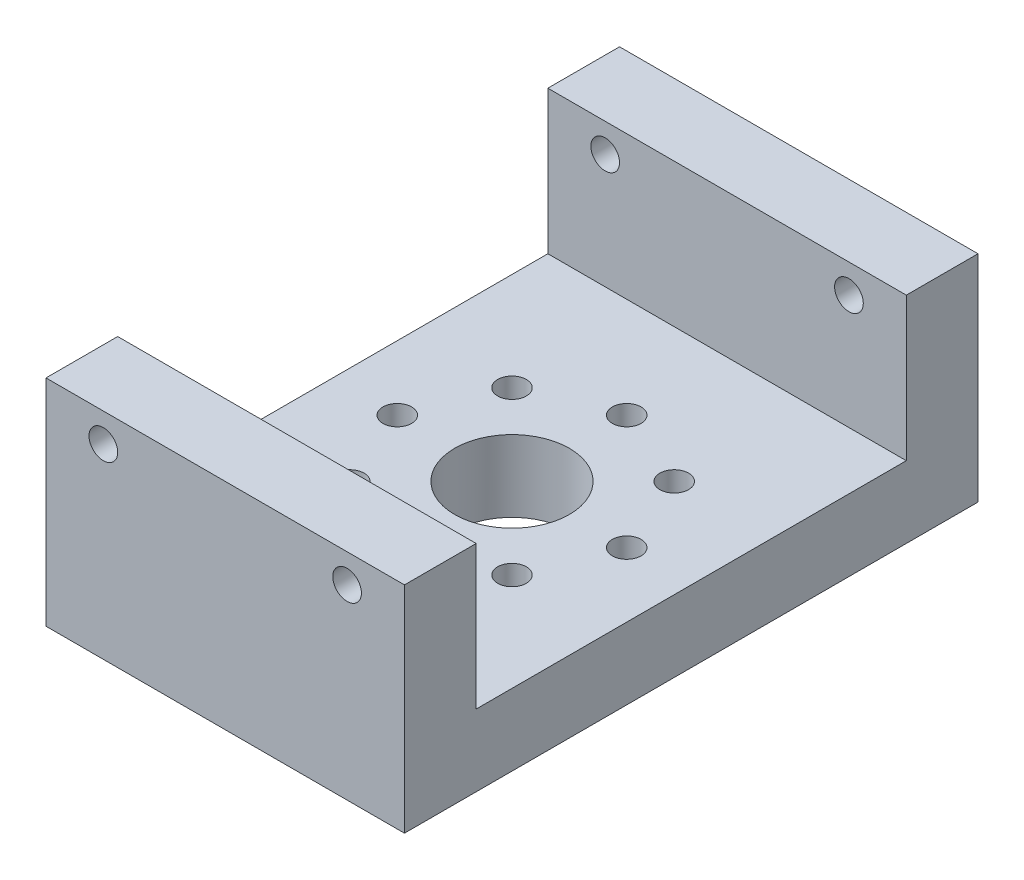
SolidWorks part; units mm, degrees
material "1060 Alloy"
ref_plane "Front Plane" through (0, 0, 0) normal (0, 0, 1) x (1, 0, 0)
ref_plane "Top Plane" through (0, 0, 0) normal (0, 1, 0) x (1, 0, 0)
ref_plane "Right Plane" through (0, 0, 0) normal (1, 0, 0) x (0, 0, -1)
sketch "Sketch1" plane through (0, 0, 0) normal (0, 1, 0) x (1, 0, 0)
  line L1 (-12.5, 20) -> (12.5, 20)
  line L2 (-12.5, 20) -> (-12.5, -20)
  line L3 (-12.5, -20) -> (12.5, -20)
  line L4 (12.5, 20) -> (12.5, -20)
  line L5 (-12.5, 20) -> (12.5, -20) construction
  line L6 (-12.5, -20) -> (12.5, 20) construction
  point P0 (0, 0)
  dimension "D1" = 40
  dimension "D2" = 25
extrude "Boss-Extrude1" add sketch "Sketch1" along normal blind 5
sketch "Sketch2" [suppressed] plane through (0, 5, 0) normal (0, 1, 0) x (1, 0, 0)
  line L0 (-5, 0) -> (5, 0) construction
  circle A0 centre (-5, 0) radius 1
  circle A1 centre (5, 0) radius 1
  point P4 (0, 0)
  dimension "D2" = 2
  dimension "D3" = 2
  dimension "D1" = 10
extrude "Cut-Extrude1" [suppressed] cut sketch "Sketch2" against normal through all
sketch "Sketch3" [suppressed] plane through (0, 5, 0) normal (0, 1, 0) x (1, 0, 0)
  circle A0 centre (-5, 0) radius 2
  circle A1 centre (5, 0) radius 2
  dimension "D1" = 4
  dimension "D2" = 4
extrude "Cut-Extrude2" [suppressed] cut sketch "Sketch3" against normal blind 2
sketch "Sketch5" plane through (0, 5, 0) normal (0, 1, 0) x (1, 0, 0)
  line L0 (12.5, -20) -> (12.5, 20) construction
  line L1 (-12.5, 20) -> (12.5, 20)
  line L2 (-12.5, 20) -> (-12.5, 15)
  line L3 (-12.5, 15) -> (12.5, 15)
  line L4 (12.5, 20) -> (12.5, 15)
  line L5 (0, 15) -> (0, -15) construction
  line L6 (-12.5, -20) -> (12.5, -20)
  line L7 (-12.5, -20) -> (-12.5, -15)
  line L8 (-12.5, -15) -> (12.5, -15)
  line L9 (12.5, -20) -> (12.5, -15)
  point P14 (0, 0)
  dimension "D1" = 30
extrude "Boss-Extrude2" add sketch "Sketch5" along normal blind 10
sketch "Sketch6" plane through (0, 0, 20) normal (0, 0, 1) x (1, 0, 0)
  line L0 (-8.5, 13) -> (8.5, 13) construction
  line L1 (0, 0) -> (0, 15) construction
  line L2 (-12.5, 15) -> (12.5, 15) construction
  circle A0 centre (-8.5, 13) radius 1
  circle A1 centre (8.5, 13) radius 1
  point P10 (0, 13)
  dimension "D1" = 2
  dimension "D2" = 2
  dimension "D3" = 17
  dimension "D4" = 2
extrude "Cut-Extrude3" cut sketch "Sketch6" against normal through all
sketch "Sketch7" plane through (0, 0, 0) normal (0, -1, 0) x (1, 0, 0)
  circle A0 centre (0, 0) radius 4
  circle A1 centre (0, 0) radius 8
  circle A2 centre (0, 8) radius 1
  circle A3 centre (5.6569, 5.6569) radius 1
  circle A4 centre (8, 0) radius 1
  circle A5 centre (5.6569, -5.6569) radius 1
  circle A6 centre (0, -8) radius 1
  circle A7 centre (-5.6569, -5.6569) radius 1
  circle A8 centre (-8, 0) radius 1
  circle A9 centre (-5.6569, 5.6569) radius 1
  point P23 (0, 0)
  dimension "D1" = 8
  dimension "D2" = 16
  dimension "D3" = 2
  dimension "D4" = 8
extrude "Cut-Extrude4" cut sketch "Sketch7" against normal blind 10 contours A1 A2 | A1 A2 | A1 A3 | A1 A3 | A1 A4 | A1 A4 | A1 A5 | A1 A5 | A1 A6 | A1 A6 | A1 A7 | A1 A7 | A1 A8 | A1 A8 | A1 A9 | A1 A9 | A0 region at (0, 0, 0) region at (7.5645, 0, 0) region at (8.413, 0, 0) region at (5.3489, 0, 5.3489) region at (5.9489, 0, 5.9489) region at (5.9489, 0, -5.9489) region at (5.3489, 0, -5.3489) region at (0, 0, 7.5645) region at (0, 0, 8.413) region at (0, 0, -8.413) region at (0, 0, -7.5645) region at (-5.3489, 0, 5.3489) region at (-5.9489, 0, 5.9489) region at (-5.9489, 0, -5.9489) region at (-5.3489, 0, -5.3489) region at (-7.5645, 0, 0) region at (-8.413, 0, 0)
